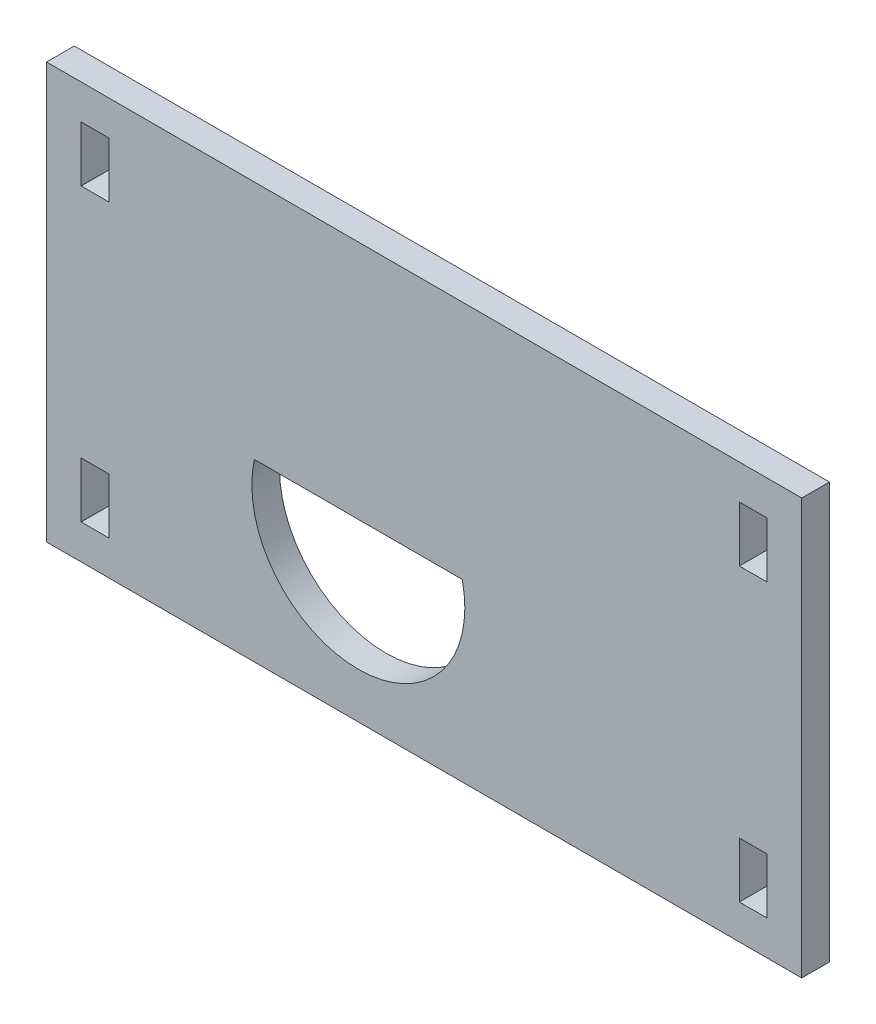
SolidWorks part; units mm, degrees
ref_plane "Front Plane" through (0, 0, 0) normal (0, 0, 1) x (1, 0, 0)
ref_plane "Top Plane" through (0, 0, 0) normal (0, 1, 0) x (1, 0, 0)
ref_plane "Right Plane" through (0, 0, 0) normal (1, 0, 0) x (0, 0, -1)
sketch "Sketch1" plane through (0, 0, 0) normal (0, 0, 1) x (1, 0, 0)
  line L0 (-15, -4.6786) -> (15, -4.6786)
  line L1 (-45, -30) -> (55, -30)
  line L3 (-45, 30) -> (55, 30)
  line L21 (0, 80.4433) -> (0, -75.6846) construction
  line L22 (36, 25) -> (40, 25) construction
  line L23 (36, 25) -> (36, 17) construction
  line L24 (36, 17) -> (40, 17) construction
  line L25 (40, 25) -> (40, 17) construction
  line L26 (-110.7456, 0) -> (128.9906, 0) construction
  line L27 (36, -17) -> (40, -17) construction
  line L28 (36, -25) -> (36, -17) construction
  line L29 (40, -25) -> (40, -17) construction
  line L30 (36, -25) -> (40, -25) construction
  line L31 (-36, -25) -> (-36, -17)
  line L32 (-36, -17) -> (-40, -17)
  line L33 (-40, -25) -> (-40, -17)
  line L34 (-36, -25) -> (-40, -25)
  line L35 (-36, 17) -> (-40, 17)
  line L36 (-36, 25) -> (-36, 17)
  line L37 (-40, 25) -> (-40, 17)
  line L38 (-36, 25) -> (-40, 25)
  line L42 (55, 30) -> (64, 30)
  line L51 (64, 30) -> (64, -30)
  line L52 (64, -30) -> (55, -30)
  line L53 (-45, 30) -> (-45, -30)
  line L54 (59, 25) -> (55, 25)
  line L55 (59, 25) -> (59, 17)
  line L56 (59, 17) -> (55, 17)
  line L57 (55, 25) -> (55, 17)
  line L58 (59, -17) -> (55, -17)
  line L59 (59, -17) -> (59, -25)
  line L60 (59, -25) -> (55, -25)
  line L61 (55, -17) -> (55, -25)
  arc A12 (-15, -4.6786) -> (15, -4.6786) centre (0, -8.0368) ccw
  point P0 (0, 0)
  dimension "D4" = 72
  dimension "D5" = 5
  dimension "D6" = 15
  dimension "D7" = 5
  dimension "D1" = 60
  dimension "D2" = 15
  dimension "D8" = 15
  dimension "D9" = 15
  dimension "D12" = 4
  dimension "D13" = 8
  dimension "D15" = 5
  dimension "D17" = 5
  dimension "D18" = 5
extrude "Boss-Extrude1" add sketch "Sketch1" along normal blind 4
